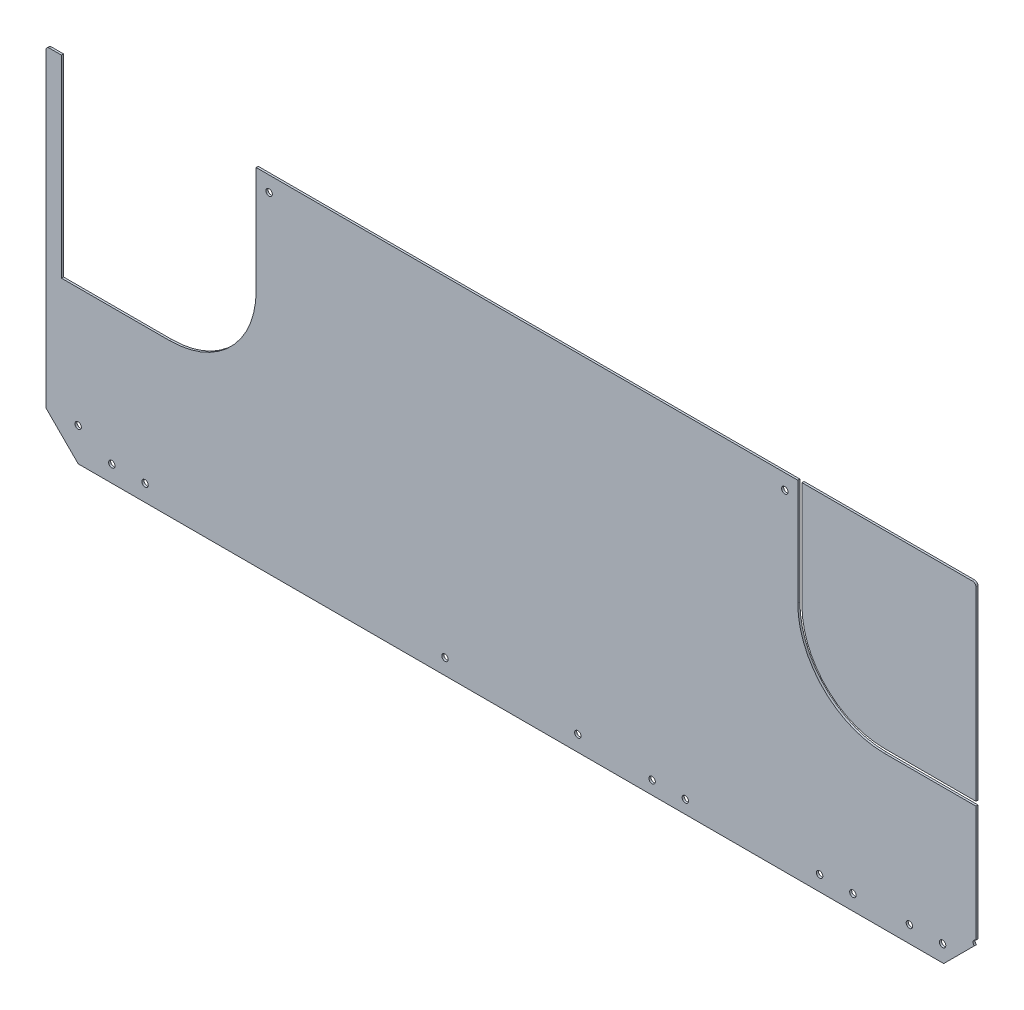
SolidWorks part; units mm, degrees
material "Perspex (TM) GS Acrylic Cast Sheet"
ref_plane "Front Plane" through (0, 0, 0) normal (0, 0, 1) x (1, 0, 0)
ref_plane "Top Plane" through (0, 0, 0) normal (0, 1, 0) x (1, 0, 0)
ref_plane "Right Plane" through (0, 0, 0) normal (1, 0, 0) x (0, 0, -1)
sketch "Sketch1" plane through (0, 0, 0) normal (0, 0, 1) x (1, 0, 0)
  line L1 (-457.2, -304.8) -> (457.2, -304.8)
  line L2 (-457.2, -304.8) -> (-457.2, 304.8)
  line L3 (-457.2, 304.8) -> (457.2, 304.8)
  line L4 (457.2, -304.8) -> (457.2, 304.8)
  line L5 (0, 304.8) -> (0, -304.8) construction
  line L6 (-457.2, 0) -> (457.2, 0) construction
  point P0 (0, 0)
  point P4 (-320.04, 0)
  point P5 (320.04, 0)
  point P6 (0, 213.36)
  point P7 (0, -213.36)
  dimension "Length" = 914.4
  dimension "Width" = 609.6
  dimension "Break" = 137.16
  dimension "D2" = 137.16
  dimension "D1" = 91.44
  dimension "D3" = 91.44
sketch "Sketch2" plane through (0, 0, 0) normal (1, 0, 0) x (0, 0, -1)
  line L0 (-0.7938, -304.8) -> (0.7938, -304.8)
  dimension "Thickness" = 1.5875
sketch "Sketch3" plane through (0, 0, 0) normal (0, 0, 1) x (1, 0, 0)
  line L0 (-457.2, -304.8) -> (-457.2, 304.8) construction
  line L1 (-457.2, -304.8) -> (457.2, -304.8) construction
  line L2 (457.2, -304.8) -> (457.2, 304.8) construction
  line L3 (-457.2, 304.8) -> (457.2, 304.8) construction
  line L4 (-457.2, -304.8) -> (-457.2, 304.8)
  line L5 (-457.2, -304.8) -> (457.2, -304.8)
  line L6 (457.2, -304.8) -> (457.2, 304.8)
  line L7 (-457.2, 304.8) -> (457.2, 304.8)
extrude "Boss-Extrude1" add sketch "Sketch3" along normal mid plane 1.5875
sketch "Sketch4" plane through (0, 0, 0.7937) normal (0, 0, 1) x (1, 0, 0)
  line L17 (-364.7412, -305.5546) -> (-390.1412, -280.1546)
  line L18 (-390.1412, -726.2421) -> (-390.1412, -40.4421) construction
  line L19 (-390.1412, -280.1546) -> (-390.1412, -42.9821)
  line L20 (-387.6012, -40.4421) -> (318.5188, -40.4421)
  line L21 (-364.7412, -305.5546) -> (295.6588, -305.5546)
  line L22 (295.6588, -65.8421) -> (295.6588, -751.6421) construction
  line L23 (295.6588, -305.5546) -> (321.0588, -280.1546)
  line L24 (321.0588, -65.8421) -> (321.0588, -751.6421) construction
  line L25 (321.0588, -280.1546) -> (321.0588, -42.9821)
  arc A0 (318.5188, -40.4421) -> (321.0588, -42.9821) centre (318.5188, -42.9821) cw
  arc A1 (-390.1412, -42.9821) -> (-387.6012, -40.4421) centre (-387.6012, -42.9821) cw
  point P17 (321.0588, -40.4421)
  point P21 (-390.1412, -40.4421)
  dimension "D1" = 2.54
  dimension "D2" = 2.54
extrude "Cut-Extrude1" cut sketch "Sketch4" against normal blind 2.54 flip side to cut
sketch "Sketch7" plane through (0, 0, 0.7937) normal (0, 0, 1) x (1, 0, 0)
  line L0 (-378.2467, -188.1903) -> (-378.2467, -39.3463)
  line L3 (-378.2467, -39.3463) -> (-229.4027, -39.3463)
  line L10 (-229.4027, -64.7463) -> (-229.4027, -39.3463)
  line L11 (-229.4027, -64.7463) -> (-229.4027, -121.8963)
  line L12 (-352.8467, -188.1903) -> (-295.6967, -188.1903)
  line L13 (-352.8467, -188.1903) -> (-378.2467, -188.1903)
  arc A1 (-229.4027, -121.8963) -> (-295.6967, -188.1903) centre (-295.6967, -121.8963) cw
extrude "Cut-Extrude2" cut sketch "Sketch7" against normal blind 2.54
sketch "Sketch8" plane through (0, 0, 0.7937) normal (0, 0, 1) x (1, 0, 0)
  line L0 (251.1151, -185.0153) -> (333.6651, -185.0153)
  line L1 (333.6651, -39.3463) -> (333.6651, -725.1463) construction
  line L2 (333.6651, -185.0153) -> (333.6651, -39.3463)
  line L3 (187.9961, -121.8963) -> (187.9961, -39.3463)
  line L4 (-378.2467, -39.3463) -> (307.5533, -39.3463) construction
  line L5 (187.9961, -39.3463) -> (333.6651, -39.3463)
  line L6 (251.1151, -188.1903) -> (336.8401, -188.1903)
  line L7 (336.8401, -188.1903) -> (336.8401, -36.1713)
  line L8 (184.8211, -36.1713) -> (336.8401, -36.1713)
  line L9 (184.8211, -121.8963) -> (184.8211, -36.1713)
  arc A0 (187.9961, -121.8963) -> (251.1151, -185.0153) centre (251.1151, -121.8963) ccw
  arc A1 (184.8211, -121.8963) -> (251.1151, -188.1903) centre (251.1151, -121.8963) ccw
  dimension "D1" = 3.175
extrude "Cut-Extrude3" cut sketch "Sketch8" against normal blind 2.54
sketch "Sketch9" plane through (0, 0, 0.7937) normal (0, 0, 1) x (1, 0, 0)
  point P0 (-365.5467, -279.4147)
  point P1 (-339.7911, -292.1147)
  point P3 (-314.3911, -292.1147)
  point P5 (-365.5467, -229.8463)
  point P15 (270.1645, -292.1147)
  point P17 (295.5645, -292.1147)
  point P19 (321.3201, -279.4147)
  point P21 (320.9651, -229.8463)
  point P23 (-219.4967, -52.0463)
  point P25 (174.9151, -52.0463)
hole_wizard "#10 (0.1935) Diameter Hole1" positions "Sketch10" profile "Sketch11" hole size "#10" standard "ANSI Inch" end condition through all
sketch "Sketch10" plane through (0, 0, 0.7937) normal (0, 0, 1) x (1, 0, 0)
  point P0 (-314.3911, -292.1147)
  point P3 (-339.7911, -292.1147)
  point P6 (-365.5467, -279.4147)
  point P21 (295.5645, -292.1147)
  point P24 (270.1645, -292.1147)
  point P27 (321.3201, -279.4147)
  point P31 (174.9151, -52.0463)
  point P34 (-219.4967, -52.0463)
  point P37 (73.3993, -294.798)
  point P40 (98.7993, -294.798)
  point P43 (201.5433, -293.2105)
  point P46 (226.9433, -293.2105)
  point P49 (-84.9856, -292.8546)
  point P52 (16.6144, -292.8546)
sketch "Sketch11" plane through (-314.3911, -292.1147, 0.7937) normal (1, 0, 0) x (0, -1, 0)
  line L0 (0, 0) -> (0, 1.5875)
  line L1 (0, 1.5875) -> (2.4574, 1.5875)
  line L2 (2.4574, 1.5875) -> (2.4574, 0)
  line L5 (2.4574, 0) -> (0, 0)
  line L11 (0, -6.35) -> (0, 107.95) construction
  dimension "Thru Hole Dia." = 4.9149
  dimension "Thru Hole Depth" = 1.5875
equation "\"D1@Boss-Extrude1\"=\"thickness@sketch2\""
equation "\"Break@Sketch1\" = \"Length@Sketch1\" * 0.15"
equation "\"D2@Sketch1\" = \"Break@Sketch1\""
equation "\"D1@Sketch1\"=\"Width@Sketch1\"*0.15"
equation "\"D3@Sketch1\"=\"D1@Sketch1\""
